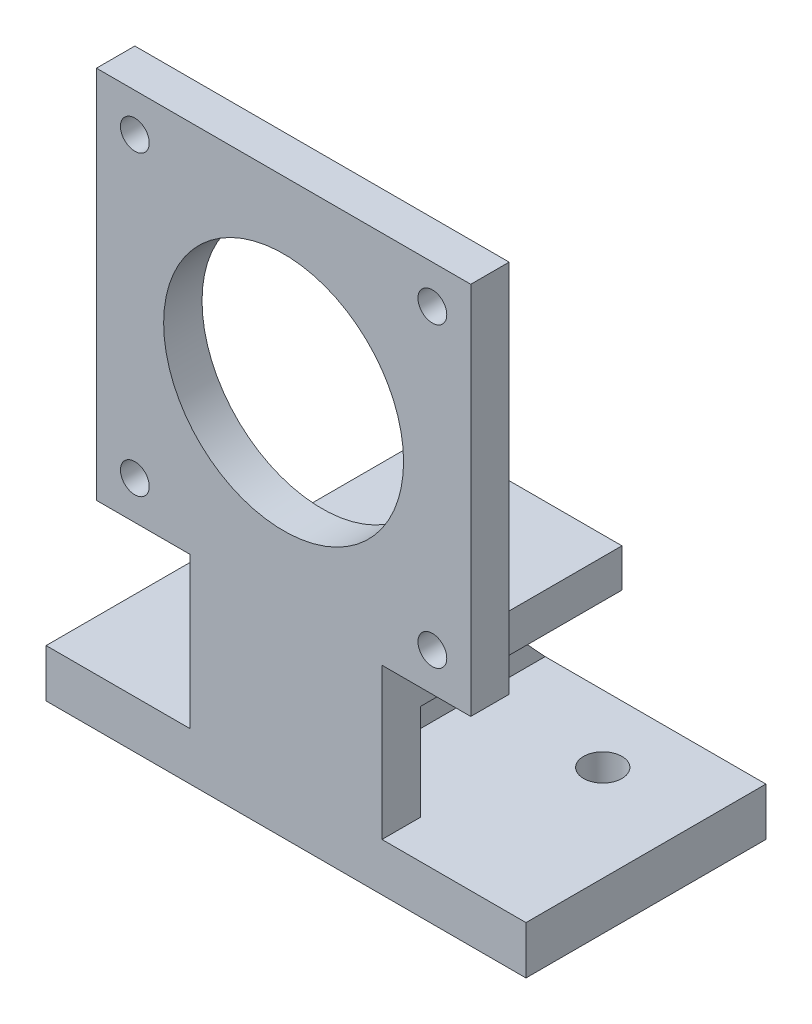
SolidWorks part; units mm, degrees
note: The reader was unsure of these and kept them because the rebuilt part matched: shared geometry of "Sketch6<3>".
ref_plane "Front Plane" through (0, 0, 0) normal (0, 0, 1) x (1, 0, 0)
ref_plane "Top Plane" through (0, 0, 0) normal (0, 1, 0) x (1, 0, 0)
ref_plane "Right Plane" through (0, 0, 0) normal (1, 0, 0) x (0, 0, -1)
sketch "Sketch1" plane through (0, 0, 0) normal (0, 0, 1) x (1, 0, 0)
  line L0 (15.2477, 15.7232) -> (-15.7523, 15.7232)
  line L1 (-10, 0) -> (10, 0)
  line L2 (-10, 0) -> (-10, -40)
  line L3 (-10, -40) -> (10, -40)
  line L4 (10, 0) -> (10, -40)
  line L5 (15.2477, 15.7232) -> (15.2477, -15.2768)
  line L6 (15.2477, -15.2768) -> (-15.7523, -15.2768)
  line L7 (-15.7523, 15.7232) -> (-15.7523, -15.2768)
  line L8 (15.2477, 15.7232) -> (-15.7523, -15.2768) construction
  line L9 (15.2477, -15.2768) -> (-15.7523, 15.7232) construction
  line L10 (19.2477, 19.7232) -> (-19.7523, 19.7232)
  line L11 (-19.7523, 19.7232) -> (-19.7523, -19.2768)
  line L12 (19.2477, -19.2768) -> (-19.7523, -19.2768)
  line L13 (19.2477, 19.7232) -> (19.2477, -19.2768)
  circle A3 centre (-0.2523, 0.2232) radius 12.5
  circle A4 centre (-15.7523, 15.7232) radius 1.5
  circle A5 centre (15.2477, 15.7232) radius 1.5
  circle A6 centre (15.2477, -15.2768) radius 1.5
  circle A7 centre (-15.7523, -15.2768) radius 1.5
  dimension "D1" = 31
  dimension "D2" = 31
  dimension "D3" = 4
  dimension "D4" = 20
  dimension "D6" = 40
extrude "Boss-Extrude1" add sketch "Sketch1" along normal blind 4
sketch "Sketch2" plane through (0, -40, 0) normal (0, -1, 0) x (1, 0, 0)
  line L0 (-10, 4) -> (10, 4) construction
  line L1 (25, 4) -> (-25, 4)
  line L2 (25, 4) -> (25, -21)
  line L3 (25, -21) -> (-25, -21)
  line L4 (-25, 4) -> (-25, -21)
  circle A0 centre (-15, -14) radius 2
  circle A1 centre (15, -14) radius 2
  point P4 (0, -21)
  dimension "D5" = 4
  dimension "D6" = 4
  dimension "D1" = 50
  dimension "D2" = 0
  dimension "D3" = 25
  dimension "D4" = 0
  dimension "D7" = 7
  dimension "D8" = 7
  dimension "D9" = 30
  dimension "D10" = 15
extrude "Boss-Extrude2" add sketch "Sketch2" against normal blind 5
sketch "Sketch5" plane through (0, 0, 0) normal (1, 0, 0) x (0, 0, -1)
  line L5 (0, 0) -> (0, -35)
  line L6 (21, -35) -> (-4, -35) construction
  line L7 (0, -35) -> (21, -35)
  line L8 (21, -35) -> (0, -12.2506)
extrude "Boss-Extrude3" add sketch "Sketch5" along normal blind 2 and the other way blind 2 contours L7 L8 L5
sketch "Sketch6" plane through (0, 0, 0) normal (0, 0, -1) x (-1, 0, 0)
  line L0 (-10, -19.2768) -> (-10, -35) construction
  line L1 (21, 21) -> (-21, 21)
  line L2 (21, 21) -> (21, -21)
  line L3 (21, -21) -> (-21, -21)
  line L4 (-21, 21) -> (-21, -21)
  line L5 (21, 21) -> (-21, -21) construction
  line L6 (21, -21) -> (-21, 21) construction
  line L7 (-10, -25) -> (10, -25)
  line L8 (-10, -25) -> (-10, -21)
  line L9 (-10, -21) -> (10, -21)
  line L10 (10, -25) -> (10, -21)
  line L11 (10, -19.2768) -> (10, -35) construction
  point P0 (0, 0)
  line M9 (2, -12.2506) -> (2, -35)
  line M11 (10, -35) -> (10, -19.2768)
  line M17 (-10, -19.2768) -> (-10, -35)
  line M19 (-2, -35) -> (-2, -12.2506)
  dimension "D1" = 42
  dimension "D2" = 42
  dimension "D3" = 4
extrude "Cut-Extrude1" cut sketch "Sketch6" along normal through all contours L1 L4 L3 L2
extrude "Boss-Extrude4" add sketch "Sketch6<3>" along normal through all contours L7 L3 M9 M11 | L7 L3 M17 M19
sketch "Sketch6<3>" plane through (0, 0, 0) normal (0, 0, -1) x (-1, 0, 0) same geometry as "Sketch6"
